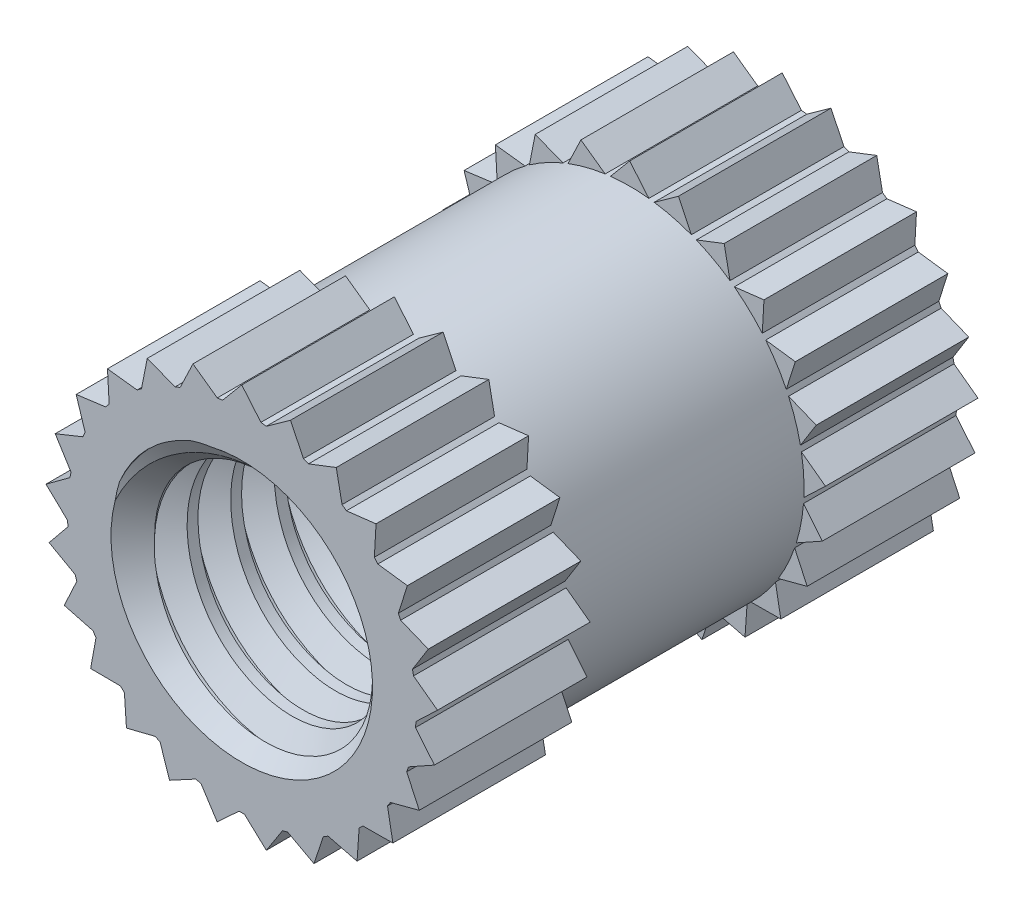
SolidWorks part; units mm, degrees
material "Brass"
ref_plane "Front Plane" through (0, 0, 0) normal (0, 0, 1) x (1, 0, 0)
ref_plane "Top Plane" through (0, 0, 0) normal (0, 1, 0) x (1, 0, 0)
ref_plane "Right Plane" through (0, 0, 0) normal (1, 0, 0) x (0, 0, -1)
sketch "Sketch1" plane through (0, 0, 0) normal (0, 0, 1) x (1, 0, 0)
  circle A1 centre (0, 0) radius 2
  dimension "D1" = 4
extrude "Boss-Extrude1" add sketch "Sketch1" along normal mid plane 6.2
hole_wizard "Tap Drill for M3x0.5 Tap1" positions "Sketch2" profile "Sketch3" hole size "M3x0.5" standard "ANSI Metric" end condition through all
sketch "Sketch2" plane through (0, 0, 3.1) normal (0, 0, 1) x (1, 0, 0)
  point P0 (0, 0)
sketch "Sketch3" plane through (0, 0, 3.1) normal (1, 0, 0) x (0, -1, 0)
  line L0 (0, 0) -> (0, 6.2)
  line L1 (0, 6.2) -> (1.5, 6.2)
  line L2 (1.25, 5.95) -> (1.25, 0.25)
  line L3 (1.25, 0.25) -> (1.5, 0)
  line L5 (1.5, 0) -> (0, 0)
  line L6 (-1.25, 0.25) -> (-1.5, 0) construction
  line L7 (1.5, 6.2) -> (1.25, 5.95)
  line L8 (-1.5, 6.2) -> (-1.25, 5.95) construction
  line L11 (0, -6.35) -> (0, 107.95) construction
  dimension "Thru Hole Dia." = 2.5
  dimension "Thru Hole Depth" = 6.2
  dimension "Near C'Sink Dia." = 3
  dimension "Near C'Sink Angle" = 90
  dimension "Far C'Sink Dia." = 3
  dimension "Far C'Sink Angle" = 90
thread "Thread1" pitch 0.5 method cut profile "Thread Profile1" start angle 0, offset 1, length 8, pitch 0.5, diameter 2.5
ref_plane "Plane1" through (-1.25, 0, 3.85) normal (0, -1, 0) x (-1, 0, 0)
sketch "Thread Profile1" plane through (-1.25, 0, 3.85) normal (0, -1, 0) x (-1, 0, 0)
  line L0 (0, 0) -> (0, 0.5) construction
  line L1 (0, 0) -> (0.2706, 0.1562)
  line L2 (0.2706, 0.1562) -> (0.2706, 0.2187)
  line L3 (0.2706, 0.2187) -> (0, 0.375)
  line L4 (0.2706, 0.1875) -> (0, 0.1875) construction
  line L11 (0, 0) -> (0, 0.375)
  point P2 (0, 0)
  dimension "Pitch" = 0.5
  dimension "Profile_Angle" = 60
  dimension "Profile_Land" = 0.0625
  dimension "Profile_Height" = 0.2706
sketch "Sketch6" plane through (0, 0, 3.1) normal (0, 0, 1) x (1, 0, 0)
  line L0 (0, 2.25) -> (0, 0) construction
  line L1 (0, 2.25) -> (-0.22, 1.9879)
  line L2 (0, 2.25) -> (0.22, 1.9879)
  circle A0 centre (0, 0) radius 2.25 construction
  circle A1 centre (0, 0) radius 2 construction
  arc A2 (0.22, 1.9879) -> (-0.22, 1.9879) centre (0, 0) ccw
  dimension "D1" = 4.5
  dimension "D2" = 80
extrude "Boss-Extrude2" add sketch "Sketch6" against normal blind 1.75
pattern_circular "CirPattern1" count 25 over 360 about axis through (0, 0, 3.1) along (0, 0, -1) of "Boss-Extrude2"
mirror "Mirror1" about plane through (0, 0, 0) normal (0, 0, 1) of "CirPattern1"
